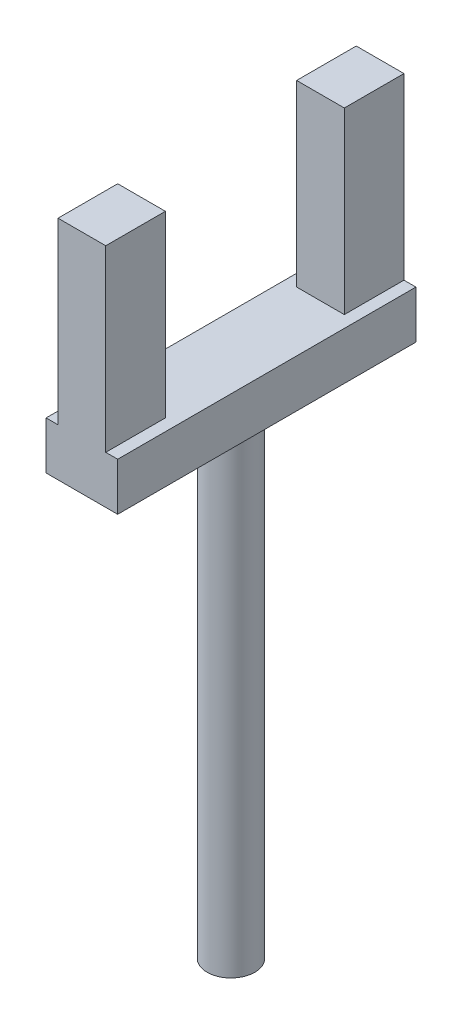
SolidWorks part; units mm, degrees
ref_plane "Front Plane" through (0, 0, 0) normal (0, 0, 1) x (1, 0, 0)
ref_plane "Top Plane" through (0, 0, 0) normal (0, 1, 0) x (1, 0, 0)
ref_plane "Right Plane" through (0, 0, 0) normal (1, 0, 0) x (0, 0, -1)
sketch "Sketch1" plane through (0, 0, 0) normal (0, 1, 0) x (1, 0, 0)
  circle A0 centre (0, 0) radius 10
  dimension "D1" = 20
extrude "Boss-Extrude1" add sketch "Sketch1" along normal blind 200
sketch "Sketch2" plane through (0, 0, 0) normal (1, 0, 0) x (0, 0, -1)
  line L0 (0, 200) -> (0, 210) construction
  line L1 (10, 200) -> (-10, 200) construction
  line L3 (-62.5, 220) -> (62.5, 220)
  line L4 (-62.5, 220) -> (-62.5, 200)
  line L5 (-62.5, 200) -> (62.5, 200)
  line L6 (62.5, 220) -> (62.5, 200)
  line L7 (-62.5, 220) -> (62.5, 200) construction
  line L8 (-62.5, 200) -> (62.5, 220) construction
  dimension "D1" = 10
  dimension "D2" = 125
extrude "Boss-Extrude2" add sketch "Sketch2" along normal blind 15 and the other way blind 15
sketch "Sketch3" plane through (0, 0, 0) normal (1, 0, 0) x (0, 0, -1)
  line L1 (-62.5, 220) -> (-37.5, 220)
  line L2 (-62.5, 220) -> (-62.5, 295)
  line L3 (-62.5, 295) -> (-37.5, 295)
  line L4 (-37.5, 220) -> (-37.5, 295)
  line L5 (62.5, 220) -> (37.5, 220)
  line L6 (62.5, 220) -> (62.5, 295)
  line L7 (62.5, 295) -> (37.5, 295)
  line L8 (37.5, 220) -> (37.5, 295)
  dimension "D1" = 25
  dimension "D2" = 75
  dimension "D3" = 75
  dimension "D4" = 25
extrude "Boss-Extrude3" add sketch "Sketch3" along normal blind 10 and the other way blind 10
ref_axis "Axis1" through (0, 200, 0) along (0, -1, 0)
ref_plane "Plane1" through (0, 100, 0) normal (0, 1, 0) x (1, 0, 0)
ref_axis "Axis2" through (0, 100, 68.75) along (0, 0, -1)
